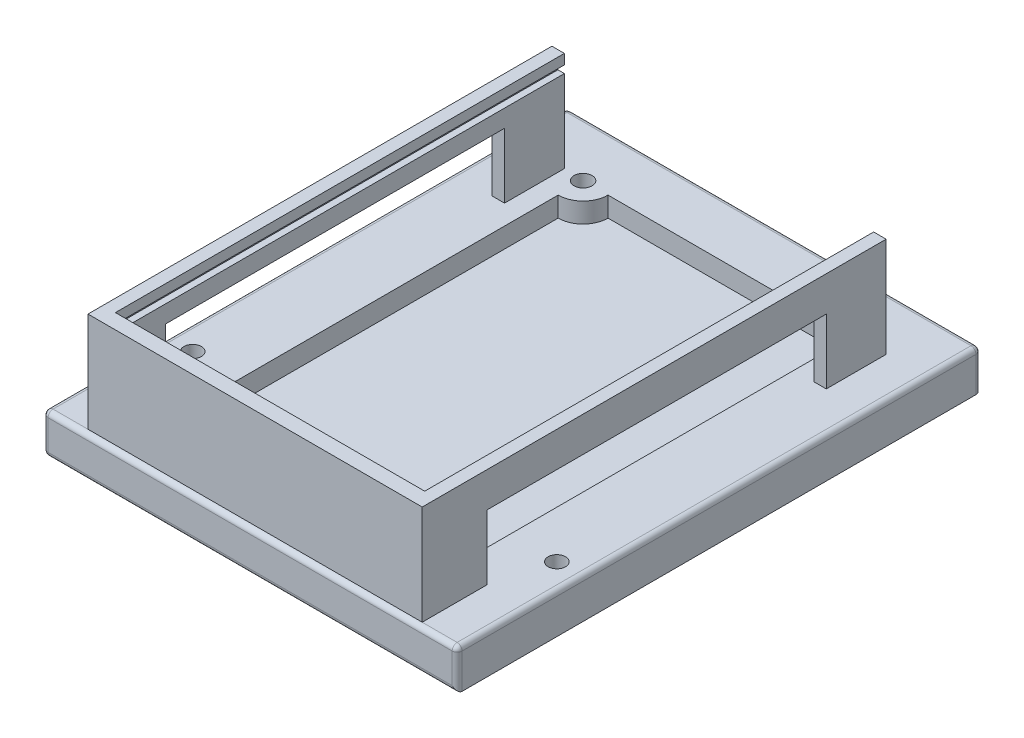
SolidWorks part; units mm, degrees
ref_plane "Front Plane" through (0, 0, 0) normal (0, 0, 1) x (1, 0, 0)
ref_plane "Top Plane" through (0, 0, 0) normal (0, 1, 0) x (1, 0, 0)
ref_plane "Right Plane" through (0, 0, 0) normal (1, 0, 0) x (0, 0, -1)
sketch "Sketch1" plane through (0, 0, 0) normal (0, 1, 0) x (1, 0, 0)
  line L0 (41.5, 95) -> (41.5, 0) construction
  line L1 (0, 0) -> (83, 0)
  line L2 (0, 0) -> (0, 105)
  line L3 (0, 105) -> (83, 105)
  line L4 (83, 0) -> (83, 105)
  line L5 (14.475, 93.775) -> (14.475, 11.225) construction
  circle A0 centre (5, 25) radius 1.75
  circle A1 centre (14.475, 11.225) radius 1.65 construction
  circle A2 centre (14.475, 93.775) radius 1.65 construction
  circle A3 centre (78, 25) radius 1.75
  circle A4 centre (68.525, 11.225) radius 1.65 construction
  circle A5 centre (68.525, 93.775) radius 1.65 construction
  point P19 (14.475, 52.5)
  point P20 (41.5, 0)
  point P21 (0, 52.5)
  dimension "D2" = 36.5
  dimension "D3" = 3.5
  dimension "D5" = 13.775
  dimension "D6" = 27.025
  dimension "D7" = 3.3
  dimension "D9" = 82.55
  dimension "D10" = 3.3
  dimension "D1" = 83
  dimension "D4" = 105
extrude "Boss-Extrude1" add sketch "Sketch1" along normal blind 8
sketch "Sketch3" plane through (0, 0, 0) normal (0, -1, 0) x (1, 0, 0)
  point P0 (14.475, -11.225)
  point P1 (68.525, -11.225)
  point P3 (68.525, -93.775)
  point P5 (14.475, -93.775)
hole_wizard "CBORE for M3 SHCS1" positions "Sketch3" profile "Sketch4" counterbore size "M3" standard "ANSI Metric" end condition through all
sketch "Sketch4" plane through (14.475, 0, -11.225) normal (1, 0, 0) x (0, 0, -1)
  line L0 (0, 0) -> (0, 8)
  line L1 (0, 8) -> (1.8, 8)
  line L3 (1.8, 8) -> (1.8, 3)
  line L4 (1.8, 3) -> (3.25, 3)
  line L5 (3.25, 3) -> (3.25, 0)
  line L7 (3.25, 0) -> (0, 0)
  line L11 (0, -6.35) -> (0, 107.95) construction
  dimension "Thru Hole Dia." = 3.6
  dimension "Thru Hole Depth" = 8
  dimension "C'Bore Dia." = 6.5
  dimension "C'Bore Depth" = 3
sketch "Sketch5" plane through (0, 8, 0) normal (0, 1, 0) x (1, 0, 0)
  line L1 (19.475, 93.775) -> (63.525, 93.775)
  line L2 (14.475, 88.775) -> (14.475, 16.225)
  line L3 (19.475, 11.225) -> (63.525, 11.225)
  line L4 (68.525, 88.775) -> (68.525, 16.225)
  line L5 (41.5, 200095) -> (41.5, -200000) construction
  circle A0 centre (14.475, 93.775) radius 1.65 construction
  circle A1 centre (14.475, 11.225) radius 1.65 construction
  arc A3 (14.475, 88.775) -> (19.475, 93.775) centre (14.475, 93.775) ccw
  arc A4 (63.525, 93.775) -> (68.525, 88.775) centre (68.525, 93.775) ccw
  arc A5 (68.525, 16.225) -> (63.525, 11.225) centre (68.525, 11.225) ccw
  arc A6 (19.475, 11.225) -> (14.475, 16.225) centre (14.475, 11.225) ccw
  dimension "D3" = 54.05
  dimension "D4" = 27.025
  dimension "D1" = 0
  dimension "D2" = 0
extrude "Cut-Extrude1" cut sketch "Sketch5" against normal blind 4
sketch "Sketch6" plane through (0, 0, 0) normal (0, -1, 0) x (1, 0, 0)
  line L1 (11.475, -40) -> (16.475, -40)
  line L2 (11.475, -40) -> (11.475, -60)
  line L3 (11.475, -60) -> (16.475, -60)
  line L4 (16.475, -40) -> (16.475, -60)
  dimension "D1" = 5
  dimension "D2" = 20
  dimension "D3" = 3
  dimension "D4" = 15
extrude "Boss-Extrude2" add sketch "Sketch6" along normal blind 8.8
sketch "Sketch7" plane through (0, 0, -60) normal (0, 0, -1) x (-1, 0, 0)
  line L0 (-16.475, -8.8) -> (-16.475, 0) construction
  line L1 (-11.475, 0) -> (-14.675, 0)
  line L2 (-11.475, 0) -> (-11.475, -6.8)
  line L3 (-11.475, -6.8) -> (-14.675, -6.8)
  line L4 (-14.675, 0) -> (-14.675, -6.8)
  dimension "D1" = 6.8
  dimension "D2" = 1.8
extrude "Cut-Extrude2" cut sketch "Sketch7" against normal through all
fillet "Fillet1" radius 6 1 edges at (16.475, 0, -50) second distance 8 first distance on face at (14.475, 0, -14.475)
fillet "Fillet2" radius 1 10 edges at (0, 4, 0) (41.5, 8, 0) (83, 4, 0) (83, 4, -105) (83, 8, -52.5) (41.5, 8, -105) (0, 4, -105) (0, 8, -52.5) (0, 0, -52.5) (41.5, 0, 0)
sketch "Sketch8" plane through (0, 8, 0) normal (0, 1, 0) x (1, 0, 0)
  line L1 (8, 94) -> (75, 94)
  line L2 (8, 94) -> (8, 1)
  line L3 (8, 1) -> (75, 1)
  line L4 (75, 94) -> (75, 1)
  line L6 (1, 1) -> (82, 1) construction
  circle A4 centre (5, 25) radius 1.75 construction
  dimension "D1" = 3
  dimension "D3" = 93
  dimension "D2" = 3
  dimension "D4" = 0
extrude "Boss-Extrude4" add sketch "Sketch8" along normal blind 20
sketch "Sketch11" plane through (0, 0, -94) normal (0, 0, -1) x (-1, 0, 0)
  line L0 (-75, 8) -> (-70.3109, 8) construction
  line L1 (-72.5, 8) -> (-10.5, 8)
  line L2 (-72.5, 8) -> (-72.5, 24.5)
  line L3 (-72.5, 28) -> (-10.5, 28)
  line L4 (-10.5, 8) -> (-10.5, 24.5)
  line L5 (-75, 28) -> (-75, 8) construction
  line L6 (-8, 28) -> (-8, 8) construction
  line L7 (-75, 28) -> (-8, 28) construction
  line L8 (-10.5, 24.5) -> (-9.2, 24.5)
  line L9 (-73.8, 26) -> (-72.5, 26)
  line L10 (-73.8, 26) -> (-73.8, 24.5)
  line L11 (-73.8, 24.5) -> (-72.5, 24.5)
  line L12 (-9.2, 26) -> (-9.2, 24.5)
  line L13 (-10.5, 26) -> (-9.2, 26)
  line L14 (-72.5, 26) -> (-72.5, 28)
  line L15 (-10.5, 26) -> (-10.5, 28)
  dimension "D1" = 2.5
  dimension "D2" = 2.5
  dimension "D3" = 0
  dimension "D4" = 1.2
  dimension "D5" = 1.5
  dimension "D6" = 1.2
  dimension "D7" = 2
extrude "Cut-Extrude3" cut sketch "Sketch11" against normal blind 90
sketch "Sketch12" plane through (0, 0, -4) normal (0, 0, -1) x (-1, 0, 0)
  line L1 (-73.8, 26) -> (-9.2, 26)
  line L2 (-73.8, 26) -> (-73.8, 24.5)
  line L3 (-73.8, 24.5) -> (-9.2, 24.5)
  line L4 (-9.2, 26) -> (-9.2, 24.5)
extrude "Cut-Extrude4" cut sketch "Sketch12" against normal blind 1
sketch "Sketch15" plane through (75, 0, 0) normal (1, 0, 0) x (0, 0, -1)
  line L0 (1, 8) -> (104, 8) construction
  line L1 (82, 8) -> (37, 8)
  line L2 (82, 8) -> (82, 21)
  line L3 (82, 21) -> (37, 21)
  line L4 (37, 8) -> (37, 21) construction
  line L5 (32, 21) -> (37, 21)
  line L6 (1, 8) -> (94, 8) construction
  line L7 (32, 8) -> (14, 8)
  line L8 (32, 8) -> (32, 21) construction
  line L9 (32, 21) -> (14, 21)
  line L10 (14, 8) -> (14, 21)
  line L11 (1, 28) -> (1, 8) construction
  line L12 (32, 8) -> (37, 8)
  dimension "D1" = 45
  dimension "D2" = 13
  dimension "D3" = 13
  dimension "D4" = 18
  dimension "D5" = 13
  dimension "D6" = 5
extrude "Cut-Extrude5" cut sketch "Sketch15" against normal through all and the other way through all
